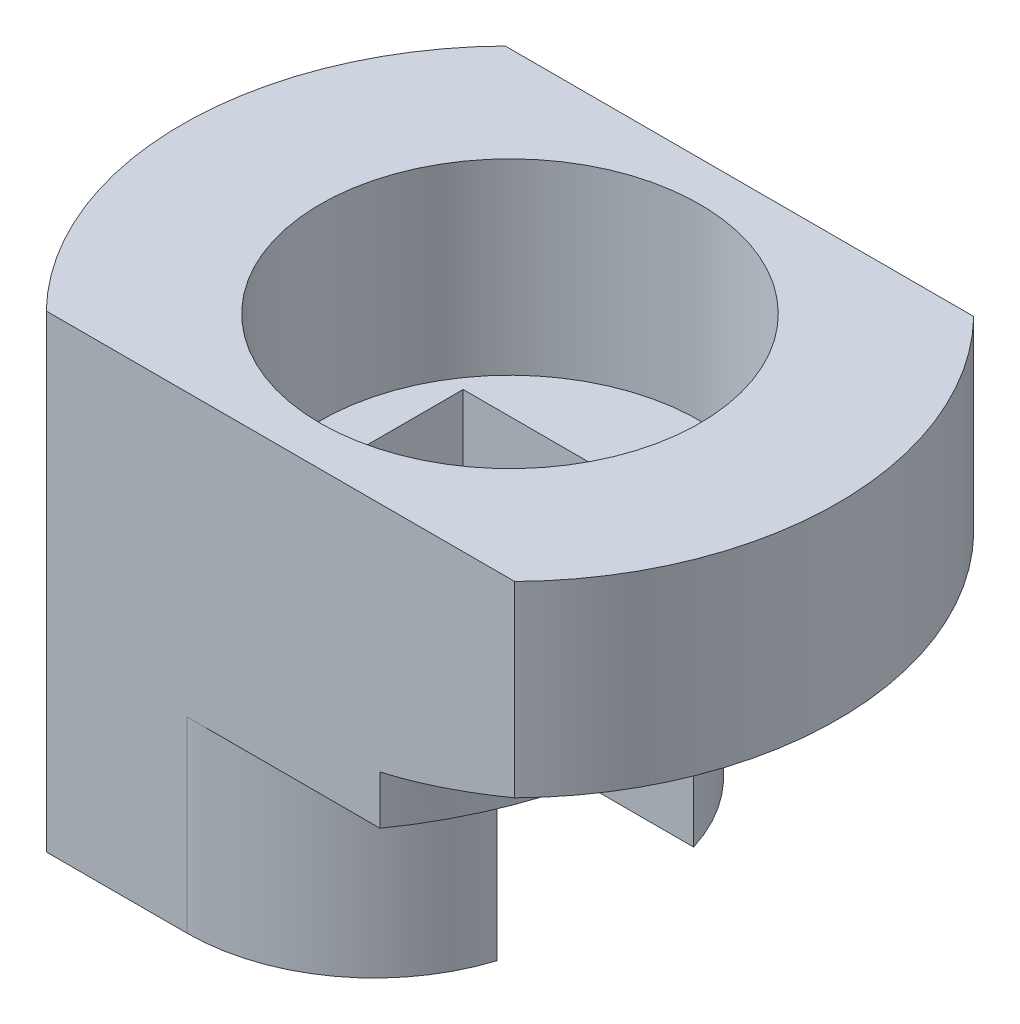
SolidWorks part; units mm, degrees
ref_plane "Спереди" through (0, 0, 0) normal (0, 0, 1) x (1, 0, 0)
ref_plane "Сверху" through (0, 0, 0) normal (0, 1, 0) x (1, 0, 0)
ref_plane "Справа" through (0, 0, 0) normal (1, 0, 0) x (0, 0, -1)
sketch "Sketch1" plane through (0, 0, 0) normal (0, 1, 0) x (1, 0, 0)
  circle A0 centre (0, 0) radius 7
  dimension "D1" = 14
extrude "Boss-Extrude3" add sketch "Sketch1" along normal blind 10
sketch "Sketch4" plane through (0, 10, 0) normal (0, 1, 0) x (1, 0, 0)
  circle A0 centre (0, 0) radius 4.05
  dimension "D1" = 8.1
extrude "Cut-Extrude1" cut sketch "Sketch4" against normal blind 4
sketch "Sketch5" plane through (0, 0, 0) normal (0, -1, 0) x (1, 0, 0)
  line L1 (3.1, 2.1) -> (-3.1, 2.1)
  line L2 (3.1, 2.1) -> (3.1, -2.1)
  line L3 (3.1, -2.1) -> (-3.1, -2.1)
  line L4 (-3.1, 2.1) -> (-3.1, -2.1)
  line L5 (3.1, 2.1) -> (-3.1, -2.1) construction
  line L6 (3.1, -2.1) -> (-3.1, 2.1) construction
  point P0 (0, 0)
  dimension "D1" = 4.2
  dimension "D2" = 6.2
extrude "Cut-Extrude2" cut sketch "Sketch5" against normal blind 6
sketch "Sketch6" plane through (0, 0, 0) normal (0, -1, 0) x (1, 0, 0)
  circle A0 centre (0, 0) radius 7 construction
  arc A1 (0, -7) -> (0, 7) centre (0, 0) ccw
  arc A2 (0, -7) -> (0, 7) centre (-4.8218, 0) ccw
  dimension "D1" = 8.5
extrude "Cut-Extrude3" cut sketch "Sketch6" against normal blind 4
sketch "Sketch7" plane through (0, 10, 0) normal (0, 1, 0) x (1, 0, 0)
  line L0 (-5, -4.899) -> (5, -4.899)
  line L1 (5, 4.899) -> (-5, 4.899)
  circle A0 centre (0, 0) radius 7 construction
  arc A1 (5, -4.899) -> (-5, -4.899) centre (0, 0) cw
  arc A2 (-5, 4.899) -> (5, 4.899) centre (0, 9.798) cw
  dimension "D1" = 10
extrude "Cut-Extrude4" cut sketch "Sketch7" against normal through all
chamfer "Chamfer1" distance 2 angle 60 1 edges at (7, 4, 0) first distance on face at (6, 7, 0)
sketch "Sketch10" plane through (0, 0, 0) normal (0, -1, 0) x (1, 0, 0)
  line L0 (1.8208, -4.899) -> (1.8208, 4.899)
  line L1 (-5, -4.899) -> (2.1244, -4.899) construction
  line L2 (2.1244, 4.899) -> (-5, 4.899) construction
  line L3 (1.8208, -4.899) -> (2.1244, -4.899)
  line L4 (1.8208, 4.899) -> (2.1244, 4.899)
  arc A0 (2.1244, -4.899) -> (2.1244, 4.899) centre (-4.8218, 0) ccw
extrude "Cut-Extrude5" cut sketch "Sketch10" against normal blind 4
fillet "Fillet1" radius 4 2 edges at (1.8208, 2, 4.899) (1.8208, 2, -4.899)
